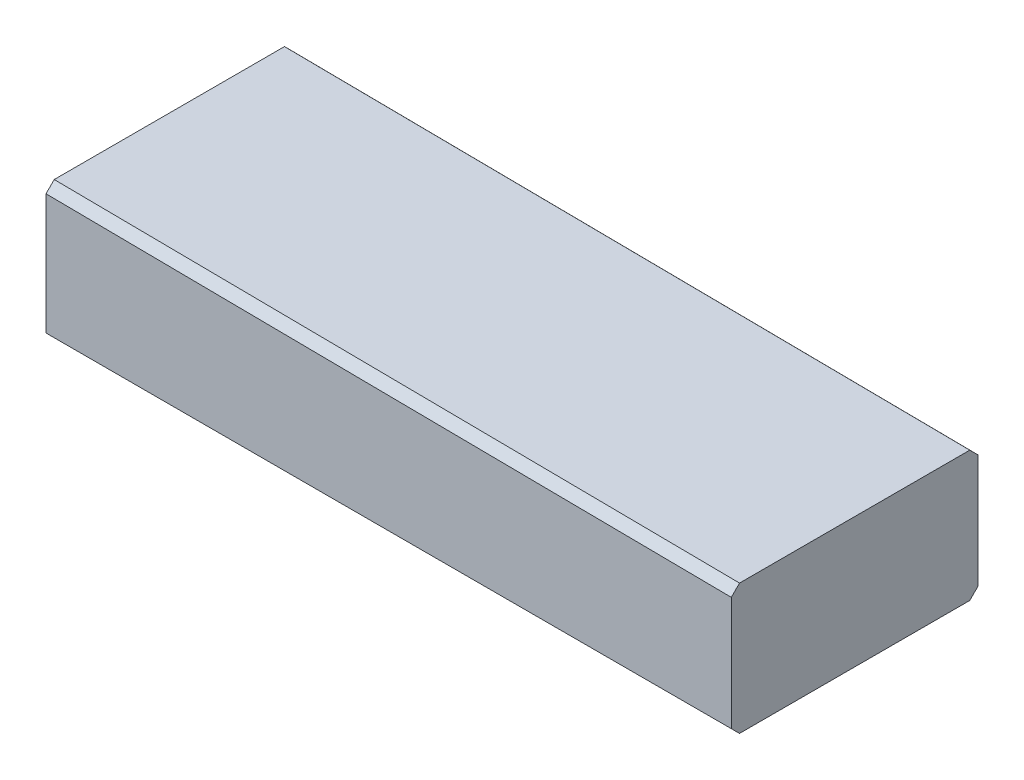
SolidWorks part; units mm, degrees
ref_plane "Front Plane" through (0, 0, 0) normal (0, 0, 1) x (1, 0, 0)
ref_plane "Top Plane" through (0, 0, 0) normal (0, 1, 0) x (1, 0, 0)
ref_plane "Right Plane" through (0, 0, 0) normal (1, 0, 0) x (0, 0, -1)
sketch "BodySke" plane through (0, 0, 0) normal (0, 0, 1) x (1, 0, 0)
  line L0 (0, 0) -> (2000, 0) construction
  line L1 (0, 0) -> (0, 20)
  line L2 (0, 20) -> (2000, 0) construction
  line L3 (100, 19) -> (100, 0)
  line L4 (100, 0) -> (0, 0)
  line L5 (0, 20) -> (100, 19)
  dimension "D2" = 2000
extrude "BaseBody" add sketch "BodySke" along normal blind 36
chamfer "Chamfer1" distance 1.2 angle 45 4 edges at (50, 19.5, 0) (50, 0, 0) (50, 0, 36) (50, 19.5, 36)
equation "\"D2@BodySke\" = \"Height@BodySke\" * 100"
